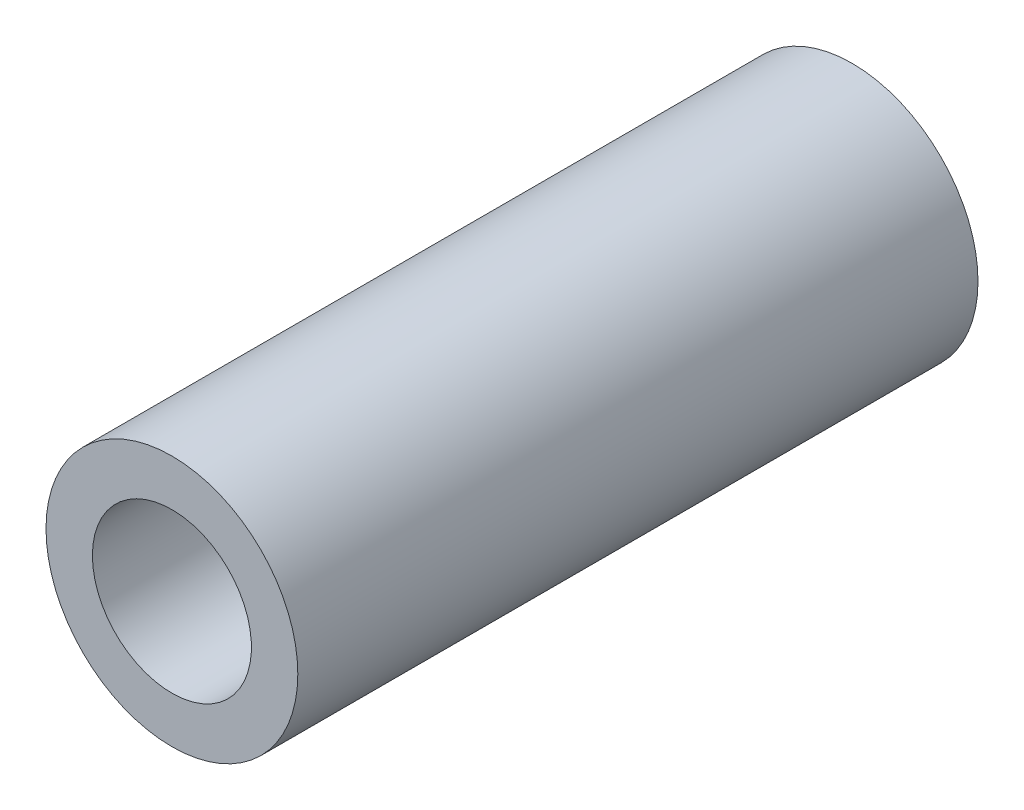
SolidWorks part; units mm, degrees
ref_plane "Front Plane" through (0, 0, 0) normal (0, 0, 1) x (1, 0, 0)
ref_plane "Top Plane" through (0, 0, 0) normal (0, 1, 0) x (1, 0, 0)
ref_plane "Right Plane" through (0, 0, 0) normal (1, 0, 0) x (0, 0, -1)
sketch "Sketch1" plane through (0, 0, 0) normal (0, 0, 1) x (1, 0, 0)
  circle A0 centre (0, 0) radius 2.375
  circle A1 centre (0, 0) radius 1.5
  dimension "OD" = 4.75
  dimension "ID" = 3
extrude "Extrude1" add sketch "Sketch1" along normal mid plane 12.83
sketch "Sketch2" plane through (0, 0, 0) normal (1, 0, 0) x (0, 0, -1)
  line L0 (-6.415, -1.5) -> (6.415, -1.5) construction
  line L3 (6.415, 1.5) -> (-6.415, 1.5) construction
  line L5 (-6.415, -1.5) -> (6.415, -1.5)
  line L6 (6.415, 1.5) -> (-6.415, 1.5)
sketch "Sketch4" plane through (0, 0, 6.415) normal (0, 0, 1) x (1, 0, 0)
  line L0 (0, 0) -> (-1.0607, 1.0607)
  line L1 (0, -2.6125) -> (0, 2.6125) construction
  circle A0 centre (0, 0) radius 1.5 construction
  dimension "D1" = 45
